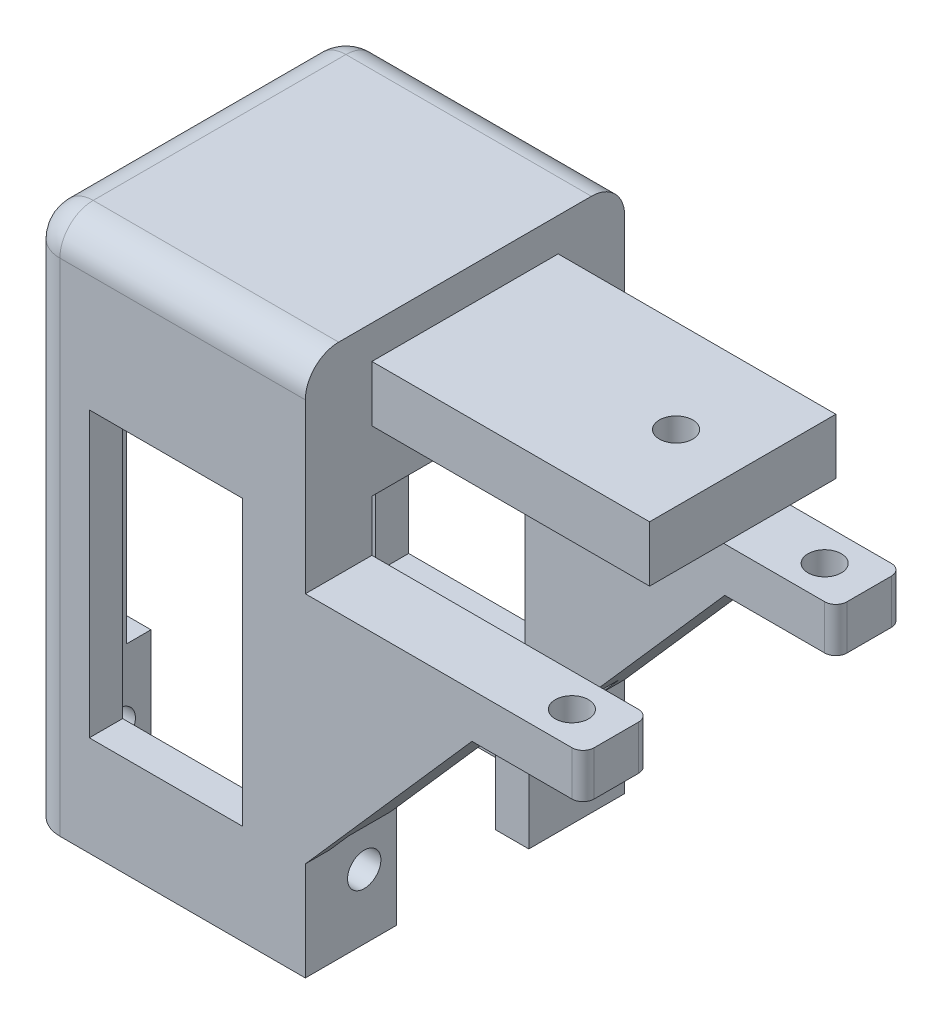
SolidWorks part; units mm, degrees
ref_plane "Front Plane" through (0, 0, 0) normal (0, 0, 1) x (1, 0, 0)
ref_plane "Top Plane" through (0, 0, 0) normal (0, 1, 0) x (1, 0, 0)
ref_plane "Right Plane" through (0, 0, 0) normal (1, 0, 0) x (0, 0, -1)
sketch "Sketch4" plane through (0, 0, 0) normal (0, 1, 0) x (1, 0, 0)
  line L1 (-12.55, 14.375) -> (12.55, 14.375)
  line L2 (-12.55, 14.375) -> (-12.55, -14.375)
  line L3 (-12.55, -14.375) -> (12.55, -14.375)
  line L4 (12.55, 14.375) -> (12.55, -14.375)
  line L5 (-12.55, 14.375) -> (12.55, -14.375) construction
  line L6 (-12.55, -14.375) -> (12.55, 14.375) construction
  point P0 (0, 0)
  dimension "D1" = 28.75
  dimension "D2" = 25.1
extrude "Boss-Extrude2" add sketch "Sketch4" along normal blind 53
sketch "Sketch5" plane through (0, 0, 0) normal (0, -1, 0) x (-1, 0, 0)
  line L0 (-12.55, -14.375) -> (-12.55, 14.375) construction
  line L1 (9.55, -11.375) -> (-9.55, -11.375)
  line L2 (9.55, -11.375) -> (9.55, 11.375)
  line L3 (9.55, 11.375) -> (-9.55, 11.375)
  line L4 (-9.55, -11.375) -> (-9.55, 11.375)
  line L5 (9.55, -11.375) -> (-9.55, 11.375) construction
  line L6 (9.55, 11.375) -> (-9.55, -11.375) construction
  line L7 (-12.55, 14.375) -> (12.55, 14.375) construction
  point P0 (0, 0)
  dimension "D1" = 22.75
  dimension "D2" = 19.1
  dimension "D3" = 3
  dimension "D4" = 3
extrude "Cut-Extrude1" cut sketch "Sketch5" against normal blind 21.67
fillet "Fillet1" radius 4.1 2 edges at (0, 21.67, -11.375) (0, 21.67, 11.375)
sketch "Sketch6" plane through (0, 21.67, 0) normal (0, -1, 0) x (-1, 0, 0)
  line L1 (2.5, 4) -> (-2.5, 4)
  line L2 (2.5, 4) -> (2.5, -4)
  line L3 (2.5, -4) -> (-2.5, -4)
  line L4 (-2.5, 4) -> (-2.5, -4)
  line L5 (2.5, 4) -> (-2.5, -4) construction
  line L6 (2.5, -4) -> (-2.5, 4) construction
  point P0 (0, 0)
  dimension "D1" = 5
  dimension "D2" = 8
extrude "Cut-Extrude2" cut sketch "Sketch6" against normal blind 4.67
sketch "Sketch7" plane through (12.55, 0, 0) normal (1, 0, 0) x (0, 0, -1)
  line L0 (-14.375, 53) -> (-14.375, 0) construction
  line L1 (-8.3848, -17.57) -> (8.3848, -17.57)
  line L2 (-8.3848, -17.57) -> (-8.3848, 17.57)
  line L3 (-8.3848, 17.57) -> (8.3848, 17.57)
  line L4 (8.3848, -17.57) -> (8.3848, 17.57)
  line L5 (-8.3848, -17.57) -> (8.3848, 17.57) construction
  line L6 (-8.3848, 17.57) -> (8.3848, -17.57) construction
  point P0 (0, 0)
  dimension "D1" = 35.14
  dimension "D2" = 5.9902
extrude "Cut-Extrude3" cut sketch "Sketch7" against normal blind 40
sketch "Sketch8" plane through (0, 0, -14.375) normal (0, 0, -1) x (-1, 0, 0)
  line L0 (12.55, 53) -> (12.55, 0) construction
  line L1 (-6.8992, -17.57) -> (6.8992, -17.57)
  line L2 (-6.8992, -17.57) -> (-6.8992, 17.57)
  line L3 (-6.8992, 17.57) -> (6.8992, 17.57)
  line L4 (6.8992, -17.57) -> (6.8992, 17.57)
  line L5 (-6.8992, -17.57) -> (6.8992, 17.57) construction
  line L6 (-6.8992, 17.57) -> (6.8992, -17.57) construction
  line L7 (-12.55, 53) -> (-12.55, 0) construction
  point P0 (0, 0)
  dimension "D1" = 35.14
  dimension "D2" = 5.6508
  dimension "D3" = 5.6508
extrude "Cut-Extrude4" cut sketch "Sketch8" against normal blind 40
sketch "Sketch9" plane through (0, 0, 0) normal (0, -1, 0) x (1, 0, 0)
  line L0 (-9.55, 8.3848) -> (-12.55, 8.3848)
  line L1 (-12.55, 8.3848) -> (-12.55, 14.375)
  line L2 (-12.55, 14.375) -> (-6.8992, 14.375)
  line L3 (-6.8992, 14.375) -> (-6.8992, 11.375)
  line L4 (-6.8992, 11.375) -> (-9.55, 11.375)
  line L5 (-9.55, 11.375) -> (-9.55, 8.3848)
  line L6 (-9.55, -8.3848) -> (-12.55, -8.3848)
  line L7 (-12.55, -8.3848) -> (-12.55, -14.375)
  line L8 (-12.55, -14.375) -> (-6.8992, -14.375)
  line L9 (-6.8992, -14.375) -> (-6.8992, -11.375)
  line L10 (-6.8992, -11.375) -> (-9.55, -11.375)
  line L11 (-9.55, -11.375) -> (-9.55, -8.3848)
  line L12 (6.8992, -11.375) -> (6.8992, -14.375)
  line L13 (6.8992, -14.375) -> (12.55, -14.375)
  line L14 (12.55, -14.375) -> (12.55, -8.3848)
  line L15 (12.55, -8.3848) -> (9.55, -8.3848)
  line L16 (9.55, -8.3848) -> (9.55, -11.375)
  line L17 (9.55, -11.375) -> (6.8992, -11.375)
  line L18 (9.55, 8.3848) -> (12.55, 8.3848)
  line L19 (12.55, 8.3848) -> (12.55, 14.375)
  line L20 (12.55, 14.375) -> (6.8992, 14.375)
  line L21 (6.8992, 14.375) -> (6.8992, 11.375)
  line L22 (6.8992, 11.375) -> (9.55, 11.375)
  line L23 (9.55, 11.375) -> (9.55, 8.3848)
extrude "Boss-Extrude3" add sketch "Sketch9" along normal blind 17
sketch "Sketch10" plane through (-6.8992, 0, 0) normal (1, 0, 0) x (0, 0, -1)
  line L0 (-11.375, 17.57) -> (-11.375, -17) construction
  line L1 (-14.375, -17) -> (-11.375, -17)
  line L2 (-14.375, -17) -> (-14.375, -8)
  line L3 (-14.375, -8) -> (-11.375, -8)
  line L4 (-11.375, -17) -> (-11.375, -8)
  dimension "D1" = 9
extrude "Boss-Extrude4" add sketch "Sketch10" along normal blind 13.8
sketch "Sketch11" plane through (6.8992, 0, 0) normal (-1, 0, 0) x (0, 0, 1)
  line L0 (-11.375, 17.57) -> (-11.375, -17) construction
  line L1 (-14.375, -17) -> (-11.375, -17)
  line L2 (-14.375, -17) -> (-14.375, -8)
  line L3 (-14.375, -8) -> (-11.375, -8)
  line L4 (-11.375, -17) -> (-11.375, -8)
  dimension "D1" = 9
extrude "Boss-Extrude5" add sketch "Sketch11" along normal blind 13.8
sketch "Sketch12" plane through (0, 0, -8.3848) normal (0, 0, 1) x (1, 0, 0)
  line L0 (-9.55, 17.57) -> (-9.55, -17) construction
  line L1 (-12.55, -17) -> (-9.55, -17)
  line L2 (-12.55, -17) -> (-12.55, -5)
  line L3 (-12.55, -5) -> (-9.55, -5)
  line L4 (-9.55, -17) -> (-9.55, -5)
  line L5 (12.55, -17) -> (12.55, 17.57) construction
  line L6 (9.55, -17) -> (12.55, -17)
  line L7 (9.55, -17) -> (9.55, -5)
  line L8 (9.55, -5) -> (12.55, -5)
  line L9 (12.55, -17) -> (12.55, -5)
  dimension "D1" = 12
  dimension "D2" = 12
extrude "Boss-Extrude6" add sketch "Sketch12" along normal blind 16.77
sketch "Sketch24" plane through (12.55, 0, 0) normal (1, 0, 0) x (0, 0, -1)
  line L1 (-8.3848, -5) -> (8.3848, -5) construction
  circle A0 centre (8.675, -11.18) radius 1.5
  circle A1 centre (-9.075, -11.18) radius 1.5
  dimension "D3" = 3
  dimension "D5" = 3
  dimension "D1" = 17.75
  dimension "D2" = 6.18
  dimension "D6" = 6.18
extrude "Cut-Extrude6" cut sketch "Sketch24" against normal blind 40.8
sketch "Sketch25" plane through (-12.55, 0, 0) normal (-1, 0, 0) x (0, 0, 1)
  line L0 (14.375, 53) -> (14.375, -17) construction
  line L1 (-14.375, 53) -> (14.375, 53)
  line L2 (-14.375, 53) -> (-14.375, 31.0749)
  line L3 (-14.375, 31.0749) -> (14.375, 31.0749)
  line L4 (14.375, 53) -> (14.375, 31.0749)
extrude "Cut-Extrude7" cut sketch "Sketch25" against normal blind 40.8
sketch "Sketch26" plane through (-12.55, 0, 0) normal (-1, 0, 0) x (0, 0, 1)
  line L0 (8.3848, -5) -> (-8.3848, -5) construction
  line L1 (-5.7417, -5) -> (6.1723, -5)
  line L2 (-5.7417, -5) -> (-5.7417, -17)
  line L3 (-5.7417, -17) -> (6.1723, -17)
  line L4 (6.1723, -5) -> (6.1723, -17)
  line L5 (14.375, -17) -> (-14.375, -17) construction
extrude "Cut-Extrude8" cut sketch "Sketch26" against normal blind 40.8
sketch "Sketch30" plane through (12.55, 0, 0) normal (1, 0, 0) x (0, 0, -1)
  line L0 (14.375, 31.0749) -> (14.375, -17) construction
  line L5 (-14.375, 31.0749) -> (14.375, 31.0749)
  line L6 (-14.375, 31.0749) -> (-14.375, 23.0549)
  line L7 (-14.375, 23.0549) -> (14.375, 23.0549)
  line L8 (14.375, 31.0749) -> (14.375, 23.0549)
  dimension "D1" = 8.02
extrude "Boss-Extrude10" add sketch "Sketch30" along normal blind 30
sketch "Sketch32" plane through (12.55, 0, 0) normal (1, 0, 0) x (0, 0, -1)
  line L0 (-14.375, 23.0549) -> (-14.375, -17) construction
  line L1 (-14.375, 12.9549) -> (-8.3848, 12.9549)
  line L2 (-14.375, 12.9549) -> (-14.375, -8.1053)
  line L3 (-14.375, -8.1053) -> (-8.3848, -8.1053)
  line L4 (-8.3848, 12.9549) -> (-8.3848, -8.1053)
  line L5 (-14.375, 23.0549) -> (14.375, 23.0549) construction
  line L6 (8.3848, -5) -> (8.3848, 17.57) construction
  line L7 (8.3848, 12.9549) -> (14.375, 12.9549)
  line L8 (8.3848, 12.9549) -> (8.3848, -8.1053)
  line L9 (8.3848, -8.1053) -> (14.375, -8.1053)
  line L10 (14.375, 12.9549) -> (14.375, -8.1053)
  line L11 (14.375, 23.0549) -> (14.375, -17) construction
  line L12 (-14.375, 23.0549) -> (14.375, 23.0549) construction
  dimension "D1" = 10.1
  dimension "D2" = 10.1
extrude "Boss-Extrude13" add sketch "Sketch32" along normal blind 30
sketch "Sketch35" plane through (0, 0, -14.375) normal (0, 0, -1) x (-1, 0, 0)
  line L0 (-42.55, 8.9549) -> (-27.55, 8.9549)
  line L1 (-42.55, -8.1053) -> (-42.55, 12.9549) construction
  line L2 (-27.55, 8.9549) -> (-12.55, -8.1053)
  line L3 (-12.55, -8.1053) -> (-42.55, -8.1053)
  line L4 (-42.55, -8.1053) -> (-42.55, 8.9549)
  line L5 (-42.55, 12.9549) -> (-12.55, 12.9549) construction
  dimension "D1" = 15
  dimension "D2" = 4
extrude "Cut-Extrude9" cut sketch "Sketch35" against normal blind 30 contours L0 L2 L3 L4
sketch "Sketch36" plane through (0, 31.0749, 0) normal (0, 1, 0) x (1, 0, 0)
  line L0 (42.55, -14.375) -> (-12.55, -14.375) construction
  line L1 (42.55, 14.375) -> (37.55, 14.375)
  line L2 (42.55, 14.375) -> (42.55, -14.375)
  line L3 (42.55, -14.375) -> (37.55, -14.375)
  line L4 (37.55, 14.375) -> (37.55, -14.375)
  dimension "D1" = 5
extrude "Cut-Extrude10" cut sketch "Sketch36" against normal blind 30 contours L4 L3 L2 L1
sketch "Sketch38" plane through (37.55, 0, 0) normal (1, 0, 0) x (0, 0, -1)
  line L0 (14.375, 23.0549) -> (-14.375, 23.0549) construction
  line L1 (-14.375, 31.0749) -> (-8.385, 31.0749)
  line L2 (-14.375, 31.0749) -> (-14.375, 23.0549)
  line L3 (-14.375, 23.0549) -> (-8.385, 23.0549)
  line L4 (-8.385, 31.0749) -> (-8.385, 23.0549)
  line L6 (14.375, 31.0749) -> (8.385, 31.0749)
  line L7 (14.375, 31.0749) -> (14.375, 23.0549)
  line L8 (14.375, 23.0549) -> (8.385, 23.0549)
  line L9 (8.385, 31.0749) -> (8.385, 23.0549)
  dimension "D1" = 5.99
  dimension "D2" = 5.99
extrude "Cut-Extrude11" cut sketch "Sketch38" against normal blind 25
sketch "Sketch39" plane through (0, 8.9549, 0) normal (0, -1, 0) x (-1, 0, 0)
  line L0 (-37.55, 8.3848) -> (-37.55, 14.375) construction
  line L1 (-37.55, -14.375) -> (-37.55, -8.3848) construction
  circle A0 centre (-33.55, 11.3799) radius 1.5
  circle A1 centre (-33.55, -11.3799) radius 1.5
  dimension "D1" = 3
  dimension "D3" = 3
  dimension "D2" = 4
  dimension "D4" = 4
extrude "Cut-Extrude12" cut sketch "Sketch39" against normal blind 25
sketch "Sketch40" plane through (0, 23.0549, 0) normal (0, -1, 0) x (1, 0, 0)
  line L0 (37.55, -8.385) -> (37.55, 8.385) construction
  circle A0 centre (31.55, 0) radius 1.5
  dimension "D2" = 3
  dimension "D1" = 6
extrude "Cut-Extrude13" cut sketch "Sketch40" against normal blind 25
fillet "Fillet4" radius 3 3 edges at (0, 31.0749, -14.375) (-12.55, 31.0749, 0) (0, 31.0749, 14.375)
fillet "Fillet5" radius 3 4 edges at (-11.6713, 30.1962, 13.4963) (-11.6713, 30.1962, -13.4963) (-12.55, 5.5375, 14.375) (-12.55, 5.5375, -14.375)
fillet "Fillet7" radius 1 4 edges at (37.55, 10.9549, 14.375) (37.55, 10.9549, 8.3848) (37.55, 10.9549, -8.3848) (37.55, 10.9549, -14.375)
sketch "Sketch41" plane through (37.55, 0, 0) normal (1, 0, 0) x (0, 0, -1)
  line L0 (8.385, 31.0749) -> (8.385, 23.0549) construction
  line L1 (-8.385, 31.0749) -> (8.385, 31.0749)
  line L2 (-8.385, 31.0749) -> (-8.385, 28.0749)
  line L3 (-8.385, 28.0749) -> (8.385, 28.0749)
  line L4 (8.385, 31.0749) -> (8.385, 28.0749)
  dimension "D1" = 3
extrude "Cut-Extrude14" cut sketch "Sketch41" against normal blind 25
sketch "Sketch43" plane through (0, 0, 8.3848) normal (0, 0, -1) x (-1, 0, 0)
  line L0 (-12.55, -8.1053) -> (-12.55, -6.1753)
  line L1 (-12.55, -6.1753) -> (-14.2469, -6.1753)
  line L2 (-12.55, -8.1053) -> (-27.55, 8.9549) construction
  line L3 (-14.2469, -6.1753) -> (-12.55, -8.1053)
  dimension "D1" = 1.93
extrude "Cut-Extrude15" cut sketch "Sketch43" against normal blind 3.79
sketch "Sketch44" plane through (0, 0, -8.3848) normal (0, 0, 1) x (1, 0, 0)
  line L0 (12.55, -8.1053) -> (12.55, -6.1753)
  line L1 (12.55, -6.1753) -> (14.2469, -6.1753)
  line L2 (27.55, 8.9549) -> (12.55, -8.1053) construction
  line L3 (14.2469, -6.1753) -> (12.55, -8.1053)
  dimension "D1" = 1.93
extrude "Cut-Extrude16" cut sketch "Sketch44" against normal blind 3.79
